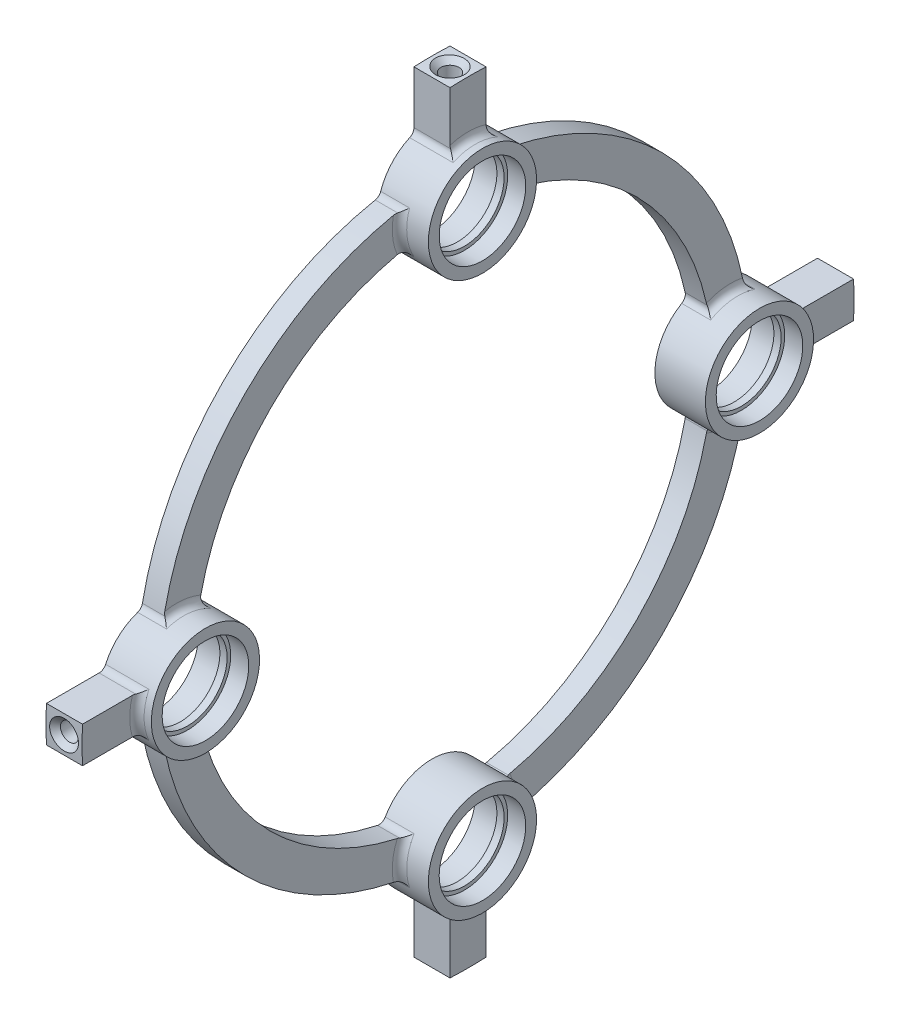
SolidWorks part; units mm, degrees
material "ABS"
ref_plane "Спереди" through (0, 0, 0) normal (0, 0, 1) x (1, 0, 0)
ref_plane "Сверху" through (0, 0, 0) normal (0, 1, 0) x (1, 0, 0)
ref_plane "Справа" through (0, 0, 0) normal (1, 0, 0) x (0, 0, -1)
sketch "Эскиз3" plane through (0, 0, 0) normal (1, 0, 0) x (0, 0, -1)
  circle A0 centre (0, 0) radius 38.4 construction
  dimension "D1" = 76.8
sketch "Эскиз1" plane through (0, 0, 0) normal (1, 0, 0) x (0, 0, -1)
  line L0 (40.9, 0) -> (35.9, 0) construction
  circle A3 centre (0, 0) radius 40.9
  circle A4 centre (0, 0) radius 35.9
  circle A5 centre (0, 0) radius 38.4 construction
  point P9 (38.4, 0)
  dimension "D1" = 5
extrude "Бобышка-Вытянуть1" add sketch "Эскиз1" along normal blind 3
sketch "Эскиз2" plane through (0, 0, 0) normal (-1, 0, 0) x (0, 0, 1)
  circle A0 centre (0, 38.4) radius 7.5
  circle A1 centre (0, 0) radius 38.4 construction
  dimension "D1" = 15
extrude "Бобышка-Вытянуть2" add sketch "Эскиз2" against normal blind 7
sketch "Эскиз4" plane through (0, 0, 0) normal (-1, 0, 0) x (0, 0, 1)
  circle A0 centre (0, 38.4) radius 5.5
  dimension "D1" = 11
extrude "Вырез-Вытянуть1" cut sketch "Эскиз4" against normal through all
sketch "Эскиз5" plane through (0, 0, 0) normal (-1, 0, 0) x (0, 0, 1)
  circle A0 centre (0, 38.4) radius 6
  dimension "D1" = 12
extrude "Вырез-Вытянуть2" cut sketch "Эскиз5" against normal blind 3.5
sketch "Эскиз6" plane through (7, 0, 0) normal (1, 0, 0) x (0, 0, -1)
  circle A0 centre (0, 38.4) radius 6
  dimension "D1" = 12
extrude "Вырез-Вытянуть3" cut sketch "Эскиз6" against normal blind 2.5
sketch "Эскиз7" plane through (0, 0, 0) normal (-1, 0, 0) x (0, 0, 1)
  line L0 (0, 0) -> (0, 53.5) construction
  line L1 (-2.5, 53.4416) -> (-2.5, 45.4711)
  line L2 (2.5, 53.4416) -> (2.5, 45.4711)
  circle A0 centre (0, 0) radius 53.5 construction
  arc A1 (7.2685, 40.249) -> (-7.2685, 40.249) centre (0, 38.4) ccw construction
  arc A2 (-2.5, 53.4416) -> (2.5, 53.4416) centre (0, 0) cw
  arc A3 (-2.5, 45.4711) -> (2.5, 45.4711) centre (0, 38.4) cw
  dimension "D1" = 107
  dimension "D2" = 5
extrude "Бобышка-Вытянуть3" add sketch "Эскиз7" against normal blind 5
fillet "Скругление1" radius 1 9 edges at (3, 37.7091, 7.4681) (3, 37.7091, -7.4681) (1.5, 35.249, -6.8059) (1.5, 35.249, 6.8059) (1.5, 40.249, 7.2685) (1.5, 40.249, -7.2685) (5, 45.9, 0) (2.5, 45.4711, 2.5) (2.5, 45.4711, -2.5)
hole_wizard "Отверстие обработанное метчиком M31" positions "Трехмерный эскиз1" profile "Эскиз8" tap size "M3" standard "ISO"
sketch3d "Трехмерный эскиз1"
  line L2 (2.5, 53.4416, 2.5) -> (2.5, 53.4416, 0) construction
  line L3 (5, 53.4416, 2.5) -> (0, 53.4416, 2.5) construction
  line L7 (2.5, 53.4416, 0) -> (2.5, 53.5, 0) construction
  line L12 (0, 53.4416, 2.5) -> (0, 53.4416, -2.5) construction
  line L13 (2.5, 53.4416, 0) -> (0, 53.4416, 0) construction
  point P0 (2.5, 53.5, 0)
  point P50 (0, 53.4416, 0)
sketch "Эскиз8" plane through (2.5, 53.5, 0) normal (1, 0, 0) x (0, 0, 1)
  line L0 (0, 0) -> (0, 7.7511)
  line L1 (0, 7.7511) -> (1.25, 7)
  line L2 (1.25, 7) -> (1.25, 0.75)
  line L3 (1.25, 0.75) -> (2, 0)
  line L5 (2, 0) -> (0, 0)
  line L6 (-1.25, 0.75) -> (-2, 0) construction
  line L10 (0, 7.7511) -> (-1.25, 7) construction
  line L11 (0, -6.35) -> (0, 107.95) construction
  dimension "Диаметр сверла" = 2.5
  dimension "Глубина сверла" = 7
  dimension "Диаметр передней зенковки" = 4
  dimension "Угол передней зенковки" = 90
  dimension "Угол заточки сверла" = 118
cosmetic thread "Отверстие резьбы1" parameters "D1"=6, "D2"=3
pattern_circular "Круговой массив1" count 4 over 360 about axis through (3, 0, 0) along (-1, 0, 0) of "Бобышка-Вытянуть2", "Вырез-Вытянуть1", "Вырез-Вытянуть2", "Вырез-Вытянуть3", "Бобышка-Вытянуть3", "Скругление1", "Отверстие обработанное метчиком M31"
